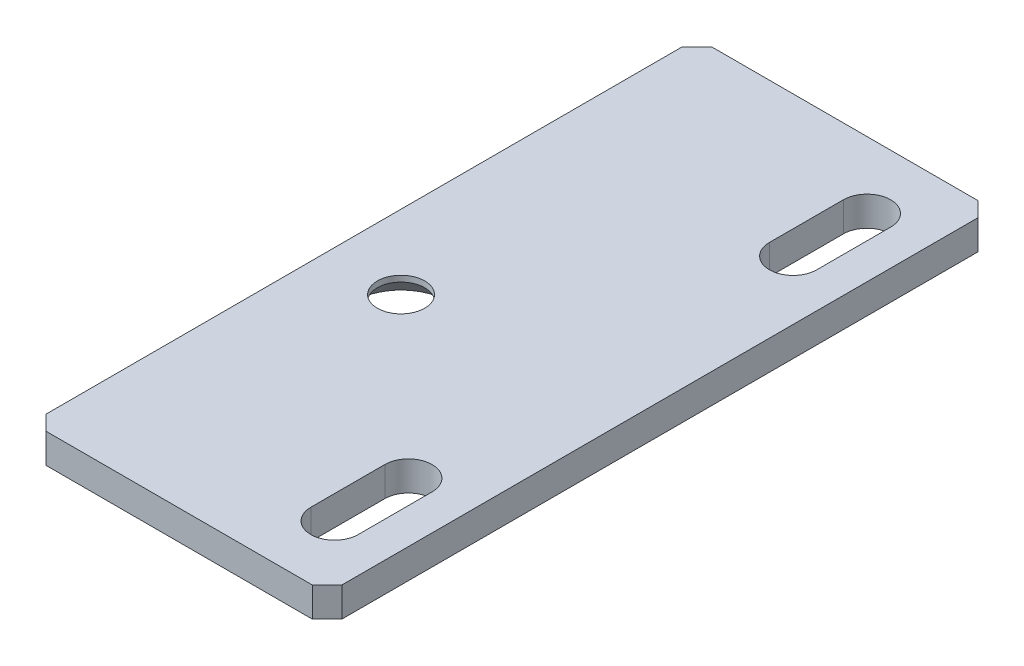
SolidWorks part; units mm, degrees
material "6061 Alloy"
ref_plane "Front Plane" through (0, 0, 0) normal (0, 0, 1) x (1, 0, 0)
ref_plane "Top Plane" through (0, 0, 0) normal (0, 1, 0) x (1, 0, 0)
ref_plane "Right Plane" through (0, 0, 0) normal (1, 0, 0) x (0, 0, -1)
sketch "Sketch1" plane through (0, 0, 0) normal (0, 1, 0) x (1, 0, 0)
  line L5 (10, -22.5) -> (-10, -22.5)
  line L6 (10, -22.5) -> (10, 22.5)
  line L7 (10, 22.5) -> (-10, 22.5)
  line L8 (-10, -22.5) -> (-10, 22.5)
  line L9 (10, -22.5) -> (-10, 22.5) construction
  line L10 (10, 22.5) -> (-10, -22.5) construction
  point P0 (0, 0)
  dimension "D3" = 20
  dimension "D4" = 45
extrude "Base" add sketch "Sketch1" along normal blind 2
sketch "Sketch6" plane through (0, 2, 0) normal (0, 1, 0) x (1, 0, 0)
  line L0 (6, 18) -> (6, 13) construction
  line L1 (7.6, 18) -> (7.6, 13)
  line L2 (4.4, 18) -> (4.4, 13)
  line L3 (6, -13) -> (6, -18) construction
  line L4 (7.6, -13) -> (7.6, -18)
  line L5 (4.4, -13) -> (4.4, -18)
  line L6 (0, 0) -> (-4.8321, 0) construction
  line L7 (10, -22.5) -> (10, 22.5) construction
  line L8 (10, 22.5) -> (-10, 22.5) construction
  arc A0 (7.6, 18) -> (4.4, 18) centre (6, 18) ccw
  arc A1 (4.4, 13) -> (7.6, 13) centre (6, 13) ccw
  arc A2 (7.6, -13) -> (4.4, -13) centre (6, -13) ccw
  arc A3 (4.4, -18) -> (7.6, -18) centre (6, -18) ccw
  point P3 (6, 15.5)
  point P8 (6, -15.5)
  dimension "D1" = 3.2
  dimension "D2" = 5
  dimension "D3" = 31
  dimension "D4" = 4
  dimension "D5" = 4.5
extrude "ScrewSlots" cut sketch "Sketch6" against normal through all
hole_wizard "PulleyHole" positions "Sketch4" profile "Sketch5" countersink size "M3" standard "ANSI Metric" end condition through all
sketch "Sketch4" plane through (0, 0, 0) normal (0, -1, 0) x (-1, 0, 0)
  line L2 (-10, -22.5) -> (-10, 22.5) construction
  line L3 (10, -22.5) -> (-10, -22.5) construction
  point P0 (5, -2.5)
  dimension "D1" = 20
  dimension "D2" = 15
sketch "Sketch5" plane through (-5, 0, 2.5) normal (1, 0, 0) x (0, 0, -1)
  line L0 (0, 0) -> (0, 2)
  line L1 (0, 2) -> (1.6, 2)
  line L2 (1.6, 2) -> (1.6, 1.6)
  line L3 (1.6, 1.6) -> (3.2, 0)
  line L5 (3.2, 0) -> (0, 0)
  line L6 (-1.6, 1.6) -> (-3.2, 0) construction
  line L11 (0, -6.35) -> (0, 107.95) construction
  dimension "Thru Hole Dia." = 3.2
  dimension "Thru Hole Depth" = 2
  dimension "Near C'Sink Dia." = 6.4
  dimension "Near C'Sink Angle" = 90
chamfer "Chamfer1" distance 1 angle 45 4 edges at (-10, 1, -22.5) (10, 1, -22.5) (10, 1, 22.5) (-10, 1, 22.5)
